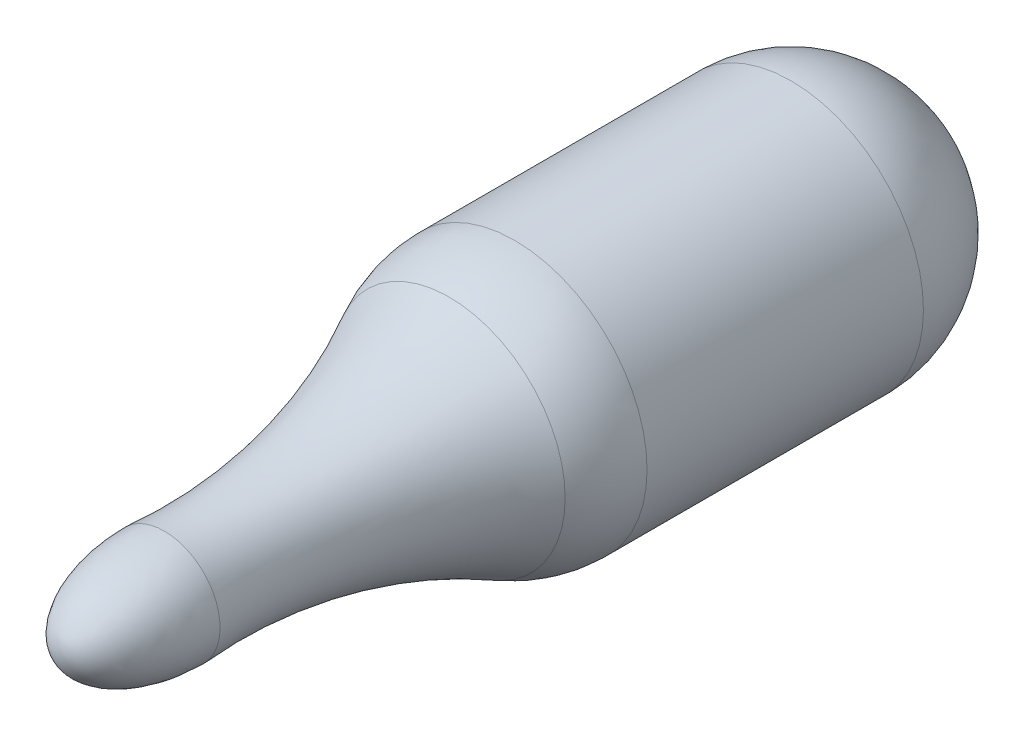
SolidWorks part; units mm, degrees
ref_plane "Front Plane" through (0, 0, 0) normal (0, 0, 1) x (1, 0, 0)
ref_plane "Top Plane" through (0, 0, 0) normal (0, 1, 0) x (1, 0, 0)
ref_plane "Right Plane" through (0, 0, 0) normal (1, 0, 0) x (0, 0, -1)
sketch "Sketch1" plane through (0, 0, 0) normal (0, 1, 0) x (0, 0, -1)
  line L0 (-15, 0) -> (109, 0)
  line L1 (0, 0) -> (90, 0) construction
  line L2 (90, 19) -> (50.3126, 19)
  line L5 (0, 0) -> (-15, 0) construction
  line L6 (90, 0) -> (109, 0) construction
  arc A0 (109, 0) -> (90, 19) centre (90, 0) ccw
  arc A1 (0, 8) -> (40.9062, 16.65) centre (5.5518, 82.7942) ccw
  arc A2 (40.9062, 16.65) -> (50.3126, 19) centre (50.3126, -1) cw
  ellipse E0 centre (0, 0) end of major axis (-15, 0) minor radius 8 (0, 8) -> (-15, 0) ccw
  point P11 (45, 19)
  dimension "D1" = 109
  dimension "D2" = 38
  dimension "D3" = 20
  dimension "D4" = 45
  dimension "D6" = 124
revolve "Revolve1" add sketch "Sketch1" angle 360 about L0
sketch "Sketch2" plane through (0, 0, 0) normal (0, 0, 1) x (1, 0, 0)
  circle A0 centre (0, 0) radius 6.35
  dimension "D1" = 12.7
extrude "Cut-Extrude2" cut sketch "Sketch2" against normal through all from offset 45 offset against normal yes
sketch "Sketch6" plane through (0, 0, -45) normal (0, 0, -1) x (-1, 0, 0)
  circle A0 centre (0, 0) radius 4.7625
  circle A1 centre (0, 0) radius 6.35
  circle A2 centre (0, 0) radius 6.35 construction
  dimension "D1" = 9.525
extrude "Boss-Extrude3" add sketch "Sketch6" along normal blind 22.86
fillet "Fillet2" radius 0.3175 4 edges at (6.35, 0, -107.9075) (-6.35, 0, -67.86) (-4.7625, 0, -67.86) (-4.7625, 0, -45)
equation "\"R75\"=92.075"
